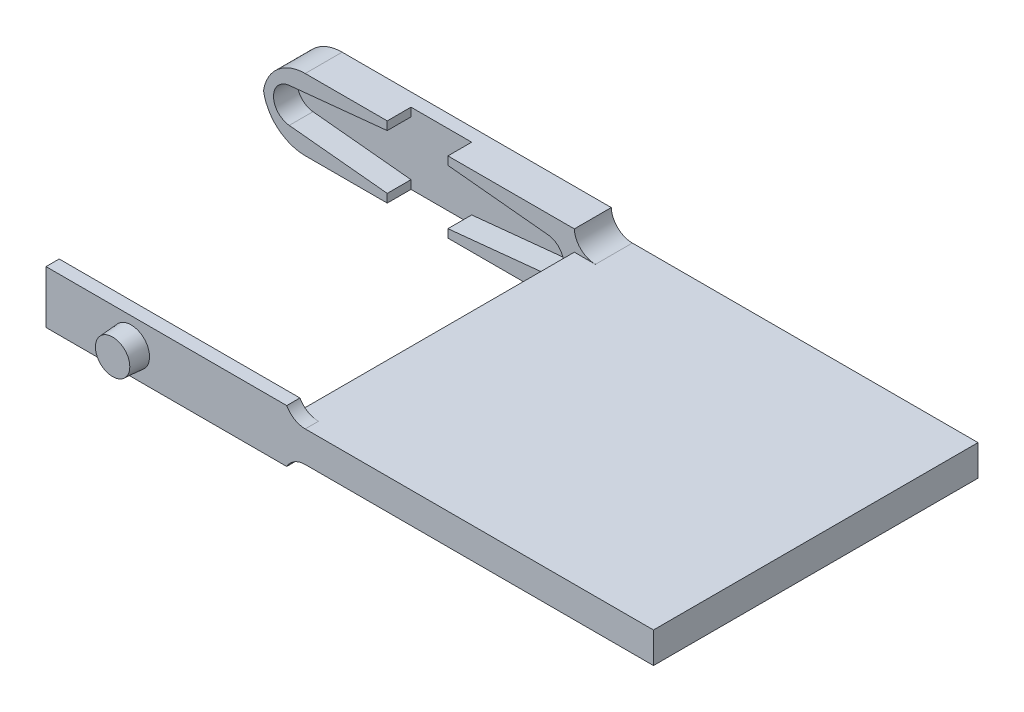
SolidWorks part; units mm, degrees
note: The reader was unsure of these and kept them because the rebuilt part matched: shared geometry of "Sketch1<16>", "Sketch1<17>", "Sketch2<9>".
ref_plane "Front Plane" through (0, 0, 0) normal (0, 0, 1) x (1, 0, 0)
ref_plane "Top Plane" through (0, 0, 0) normal (0, 1, 0) x (1, 0, 0)
ref_plane "Right Plane" through (0, 0, 0) normal (1, 0, 0) x (0, 0, -1)
ref_plane "Ground Plane" through (0, 0, 29.25) normal (0, 0, -1) x (-1, 0, 0)
sketch "Sketch1" plane through (0, 0, 0) normal (0, 0, 1) x (1, 0, 0)
  line L0 (0, 3.375) -> (-13.75, 3.375) construction
  line L1 (0, 3.375) -> (0, 6.25) construction
  line L2 (-12.2651, 5.0167) -> (0, 6.25)
  line L3 (-13.75, 3.375) -> (-13.75, 1.1142) construction
  line L4 (-12.2651, 1.7333) -> (0, 0.5)
  line L5 (12.2651, 1.7333) -> (0, 0.5)
  line L6 (12.2651, 5.0167) -> (0, 6.25)
  line L7 (-2.875, 3.375) -> (-2.875, -5.5898) construction
  line L8 (-14.75, 0) -> (14.75, 0)
  line L9 (-14.75, 0) -> (-14.75, 6.75)
  line L10 (-14.75, 6.75) -> (14.75, 6.75)
  line L11 (-43.5503, 24.4221) -> (7.9447, 11.3967) construction
  line L12 (13.75, 3.375) -> (13.75, 0.9067) construction
  line L13 (14.75, 4.8371) -> (49.5, 4.8371)
  line L14 (14.5, 4.8371) -> (14.5, 1.9129) construction
  line L15 (14.75, 1.9129) -> (49.5, 1.9129)
  line L16 (49.5, 4.8371) -> (49.5, 1.9129)
  line L17 (-43.5503, 24.4221) -> (7.9447, 11.3967)
  line L18 (14.75, 6.75) -> (14.75, 0)
  line L19 (8.1899, 12.3661) -> (3.8863, -4.648) construction
  line L20 (8.1899, 12.3661) -> (3.8863, -4.648)
  line L21 (8.1899, 12.3661) -> (3.8863, -4.648)
  line L22 (8.1899, 12.3661) -> (3.8863, -4.648) construction
  line L23 (8.1899, 12.3661) -> (3.8863, -4.648)
  circle A0 centre (0, 3.375) radius 2.875 construction
  arc A1 (-12.2651, 5.0167) -> (-12.2651, 1.7333) centre (-12.1, 3.375) ccw
  arc A2 (12.2651, 5.0167) -> (12.2651, 1.7333) centre (12.1, 3.375) cw
  circle A3 centre (-12.1, 3.375) radius 0.2914
  circle A4 centre (-10.0632, 3.375) radius 0.2914
  circle A5 centre (-8.0264, 3.375) radius 0.2914
  circle A6 centre (8.0264, 3.375) radius 0.2914
  circle A7 centre (10.0632, 3.375) radius 0.2914
  circle A8 centre (12.1, 3.375) radius 0.2914
  point P2 (-14.75, 3.375)
  point P27 (0, 6.75)
  point P34 (14.5, 3.375)
  point P35 (49.5, 3.375)
  dimension "D1" = 5.75
  dimension "D9" = 1.65
  dimension "D3" = 2.9241
  dimension "D5" = 29.5
  dimension "D7" = 6.75
  dimension "D8" = 1.7333
  dimension "D11" = 27.5
  dimension "D6" = 13.75
  dimension "D2" = 3
extrude "Boss-Extrude10" add sketch "Sketch1" along normal blind 3.5
extrude "Boss-Extrude15" add sketch "Sketch1<16>" along normal blind 1.25 contours A7 | A8 | A4 | A5 | A3 | L2 A1 L4 A0 A5 A4 A3 | L2 A0 L4 L5 L6 | A2 L6 A0 L5 A7 A6 A8 | A6
sketch "Sketch1<16>" plane through (0, 0, 0) normal (0, 0, 1) x (1, 0, 0) same geometry as "Sketch1"
extrude "Boss-Extrude17" add sketch "Sketch1<17>" along direction (0, 0, -1) on the side of the normal offset from surface (30.75 mm away) 1.5 contours L13 L18 L15 L16
sketch "Sketch1<17>" plane through (0, 0, 0) normal (0, 0, 1) x (1, 0, 0) same geometry as "Sketch1"
sketch "Sketch2" plane through (0, 0, 30.75) normal (0, 0, 1) x (1, 0, 0)
  line L0 (0, 2.75) -> (0, 3.375) construction
  line L1 (13.5, 5.875) -> (-8.0614, 5.875)
  line L3 (14.75, 0.875) -> (-8.0614, 0.875)
  line L4 (-8.0614, 5.875) -> (-8.0614, 0.875)
  line L6 (14.75, 4.8371) -> (14.75, 1.9129) construction
  line L7 (13.5, 5.875) -> (14.75, 5.875)
  line L8 (14.75, 5.875) -> (14.75, 0.875)
  circle A0 centre (0, 3.375) radius 1.75
  circle A3 centre (0, 3.375) radius 2.875 construction
  point P12 (14.5, 3.375)
  dimension "D1" = 3.5
  dimension "D2" = 5
extrude "Boss-Extrude18" add sketch "Sketch2" against normal blind 1.25 contours L1 L4 L3 L8 L7
extrude "Boss-Extrude19" add sketch "Sketch2<9>" along normal blind 1.75 draft 4 contours A0
sketch "Sketch2<9>" plane through (0, 0, 30.75) normal (0, 0, 1) x (1, 0, 0) same geometry as "Sketch2"
fillet "Fillet1" radius 2 4 edges at (14.75, 1.9129, 30.125) (14.75, 4.8371, 30.125)
fillet "Fillet2" radius 4 2 edges at (-14.75, 6.75, 1.75) (-14.75, 0, 1.75)
sketch "Sketch3" plane through (0, 0, 3.5) normal (0, 0, 1) x (1, 0, 0)
  line L0 (-0.1021, 0) -> (-0.1021, 6.75) construction
  line L1 (-2.9771, 6.75) -> (-2.9771, 0) construction
  line L3 (-10.75, 6.75) -> (14.75, 6.75) construction
  line L4 (-14.7009, 3.375) -> (-0.1021, 3.375) construction
  line L5 (2.7729, 6.75) -> (2.7729, 0) construction
  line L6 (2.7729, 6.75) -> (2.7729, 5.625)
  line L7 (-2.9771, 5.625) -> (2.7729, 5.625)
  line L8 (-2.9771, 0) -> (2.7729, 0)
  line L9 (-2.9771, 0) -> (-2.9771, 1.125)
  line L10 (-2.9771, 1.125) -> (2.7729, 1.125)
  line L11 (2.7729, 0) -> (2.7729, 1.125)
  line L12 (-2.9771, 6.75) -> (2.7729, 6.75)
  line L13 (-2.9771, 6.75) -> (-2.9771, 5.625)
  line L19 (-10.75, 0) -> (14.75, 0) construction
  circle A0 centre (-0.1021, 3.375) radius 2.875 construction
  circle A1 centre (-0.1021, 3.375) radius 2.875 construction
  circle A2 centre (-0.1021, 3.375) radius 2.25 construction
  circle A3 centre (-0.1021, 3.375) radius 2.25 construction
extrude "Cut-Extrude1" cut sketch "Sketch3" against normal up to surface (2.25 mm away)
equation "\"D5@Sketch1\"=\"D6@Sketch1\"*2+2"
